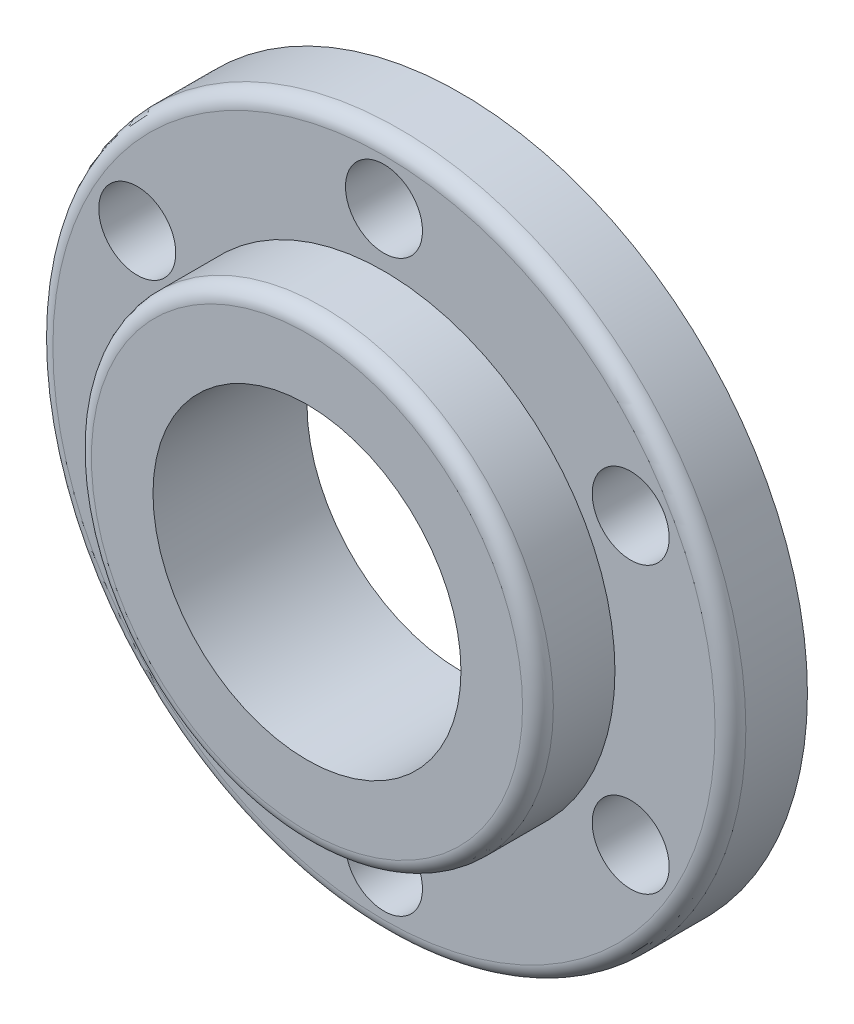
SolidWorks part; units mm, degrees
material "普通碳钢"
ref_plane "Front Plane" through (0, 0, 0) normal (0, 0, 1) x (1, 0, 0)
ref_plane "Top Plane" through (0, 0, 0) normal (0, 1, 0) x (1, 0, 0)
ref_plane "Right Plane" through (0, 0, 0) normal (1, 0, 0) x (0, 0, -1)
sketch "Sketch1" plane through (0, 0, 0) normal (0, 0, 1) x (1, 0, 0)
  line L0 (0, 45) -> (0, -45) construction
  line L1 (-45, 0) -> (45, 0) construction
  circle A0 centre (0, 0) radius 45
  circle A1 centre (0, 0) radius 37 construction
  circle A2 centre (0, 37) radius 5
  circle A3 centre (32.0429, 18.5) radius 5
  circle A4 centre (0, 0) radius 37 construction
  circle A5 centre (32.0429, -18.5) radius 5
  circle A6 centre (0, 0) radius 37 construction
  circle A7 centre (0, -37) radius 5
  circle A8 centre (0, 0) radius 37 construction
  circle A9 centre (-32.0429, -18.5) radius 5
  circle A10 centre (0, 0) radius 37 construction
  circle A11 centre (-32.0429, 18.5) radius 5
  circle A12 centre (0, 0) radius 37 construction
  circle A13 centre (0, 0) radius 30
  circle A14 centre (0, 0) radius 20
  point P27 (0, 0)
  dimension "D1" = 90
  dimension "D2" = 74
  dimension "D3" = 10
  dimension "D5" = 60
  dimension "D6" = 40
  dimension "D4" = 6
extrude "Boss-Extrude1" add sketch "Sketch1" along normal blind 10 contours A0 A13 A11 A9 A7 A5 A3 A2 region at (-43.7272, 0, 0)
extrude "Boss-Extrude2" add sketch "Sketch1<3>" along normal blind 20 contours A13 A14 region at (-29.1515, 0, 0)
sketch "Sketch1<3>" plane through (0, 0, 0) normal (0, 0, 1) x (1, 0, 0) same geometry as "Sketch1"
fillet "Fillet1" radius 2 2 edges at (45, 0, 10) (30, 0, 20)
scale "缩放比例1" scale about centroid uniform scaling yes scale factor 0.135065
